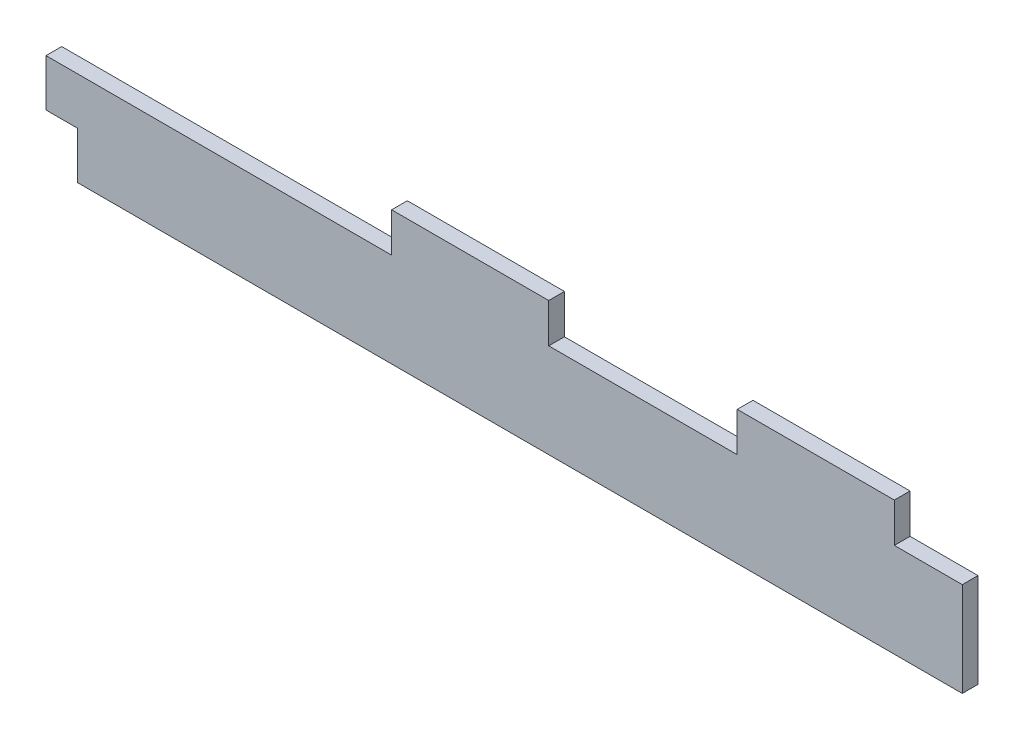
SolidWorks part; units mm, degrees
ref_plane "Front Plane" through (0, 0, 0) normal (0, 0, 1) x (1, 0, 0)
ref_plane "Top Plane" through (0, 0, 0) normal (0, 1, 0) x (1, 0, 0)
ref_plane "Right Plane" through (0, 0, 0) normal (1, 0, 0) x (0, 0, -1)
sketch "Sketch1" plane through (0, 0, 0) normal (0, 0, 1) x (1, 0, 0)
  line L0 (49, 15) -> (73, 15)
  line L1 (-11, 3) -> (101.65, 3)
  line L2 (-15, 9) -> (-15, 15)
  line L3 (-15, 15) -> (29, 15)
  line L4 (101.65, 3) -> (101.65, 15)
  line L6 (29, 15) -> (29, 20)
  line L7 (29, 20) -> (49, 20)
  line L8 (49, 15) -> (49, 20)
  line L10 (73, 15) -> (73, 20)
  line L11 (73, 20) -> (93, 20)
  line L12 (93, 15) -> (93, 20)
  line L15 (-15, 9) -> (-11, 9)
  line L16 (-11, 3) -> (-11, 9)
  line L17 (93, 15) -> (101.65, 15)
  dimension "D1" = 12
  dimension "D2" = 116.65
  dimension "D3" = 44
  dimension "D4" = 20
  dimension "D5" = 24
  dimension "D6" = 20
  dimension "D7" = 4
  dimension "D8" = 6
  dimension "D9" = 5
base flange "Base-Flange1" sketch "Sketch1" thickness 2 reverse thickness direction no parameters "D1"=2
sketch "Bend-Lines1" [suppressed] plane through (0, 0, 0) normal (0, 1, 0) x (1, 0, 0)
sketch "Bounding-Box1" [suppressed] plane through (0, 0, 0) normal (0, 1, 0) x (1, 0, 0)
sheet metal parameters "Sheet-Metal1" thickness 2 parameters "D1"=2
flat pattern "Flat-Pattern1" [suppressed]
sketch "Bend-Lines2" plane through (0, 0, 0) normal (0, 1, 0) x (1, 0, 0)
sketch3d "Bounding-Box2" [suppressed]
  line L0 (-15, 3, 0) -> (101.65, 3, 0) construction
  line L1 (-15, 20, 0) -> (101.65, 20, 0) construction
  line L2 (-15, 3, 0) -> (-15, 20, 0) construction
  line L3 (101.65, 3, 0) -> (101.65, 20, 0) construction
equation "\"D6@Sketch1\"=\"D4@Sketch1\""
